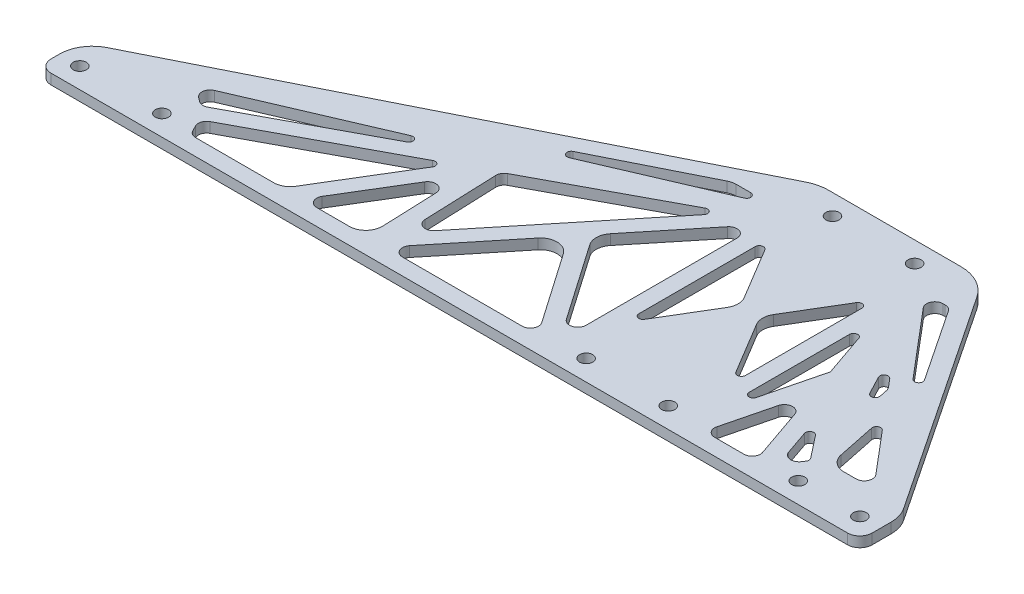
SolidWorks part; units mm, degrees
ref_plane "Front Plane" through (0, 0, 0) normal (0, 0, 1) x (1, 0, 0)
ref_plane "Top Plane" through (0, 0, 0) normal (0, 1, 0) x (1, 0, 0)
ref_plane "Right Plane" through (0, 0, 0) normal (1, 0, 0) x (0, 0, -1)
sketch "Sketch1" plane through (0, 0, 0) normal (0, 1, 0) x (1, 0, 0)
  line L0 (0, 0) -> (254, 0)
  line L2 (203.2, 88.9) -> (152.4, 88.9)
  line L4 (0, 0) -> (0, 12.7)
  line L5 (0, 12.7) -> (152.4, 88.9)
  line L6 (203.2, 88.9) -> (254, 12.7)
  line L7 (254, 12.7) -> (254, 0)
  line L8 (0, 6.35) -> (41.2306, 6.35) construction
  line L9 (254, 6.35) -> (220.1675, 6.35) construction
  line L10 (139.7, 82.55) -> (207.4333, 82.55) construction
  line L11 (156.6333, 76.2) -> (38.0113, 12.7) construction
  line L12 (38.0113, 12.7) -> (22.7185, 24.0592)
  line L13 (226.5259, 15.8112) -> (251.9259, 15.8112)
  line L20 (127, 76.2) -> (211.6667, 76.2)
  line L21 (226.5259, 15.8112) -> (215.9, 0)
  line L22 (38.0113, 12.7) -> (44.45, 0)
  line L23 (156.6333, 76.2) -> (27.2885, 20.6647) construction
  line L24 (156.6333, 76.2) -> (98.8302, 5.08) construction
  line L28 (194.7333, 76.2) -> (226.5259, 15.8112) construction
  line L31 (5.08, 9.5604) -> (153.5992, 83.82)
  line L32 (200.4813, 83.82) -> (153.5992, 83.82)
  line L33 (200.4813, 83.82) -> (248.92, 11.1619)
  line L34 (248.92, 11.1619) -> (248.92, 5.08)
  line L35 (5.08, 5.08) -> (248.92, 5.08)
  line L36 (5.08, 5.08) -> (5.08, 9.5604)
  line L37 (219.314, 5.08) -> (194.7333, 76.2) construction
  line L39 (194.7333, 76.2) -> (245.8205, 15.8112) construction
  line L40 (98.8302, 5.08) -> (97.3223, 44.45) construction
  line L41 (127.7318, 40.64) -> (152.3892, 5.08) construction
  line L42 (207.0237, 40.64) -> (198.1092, 5.08) construction
  line L83 (226.5259, 15.8112) -> (220.2769, 46.0056) construction
  line L84 (207.0237, 40.64) -> (226.5259, 15.8112) construction
  line L107 (97.3223, 44.45) -> (73.4302, 5.08) construction
  line L108 (156.6333, 76.2) -> (194.7333, 12.7) construction
  line L113 (194.7333, 76.2) -> (156.6333, 12.7) construction
  line L114 (155.6312, 78.534) -> (26.2864, 22.9986)
  line L115 (155.4346, 78.4393) -> (36.8125, 14.9393)
  line L116 (154.6622, 77.802) -> (101.1104, 11.9127)
  line L117 (156.6333, 12.7) -> (154.0933, 8.1397)
  line L118 (156.6333, 12.7) -> (194.7333, 12.7)
  line L119 (194.7333, 12.7) -> (200.3598, 0)
  line L120 (153.0965, 6.35) -> (197.5465, 6.35) construction
  line L123 (101.1104, 11.9127) -> (99.5369, 52.9951)
  line L124 (99.5369, 52.9951) -> (96.1931, 47.4852)
  line L125 (125.6445, 39.1927) -> (150.3019, 3.6327)
  line L126 (192.5553, 77.5068) -> (154.4553, 14.0068)
  line L127 (154.4553, 74.8932) -> (192.5553, 11.3932)
  line L128 (156.6333, 12.7) -> (156.6333, 76.2) construction
  line L129 (194.7333, 12.7) -> (194.7333, 76.2) construction
  line L130 (197.2733, 12.7) -> (197.2733, 76.2)
  line L131 (159.1733, 12.7) -> (159.1733, 76.2)
  line L132 (192.1933, 12.7) -> (192.1933, 76.2)
  line L133 (154.0933, 12.7) -> (154.0933, 76.2)
  line L134 (205.8201, 46.2844) -> (228.5234, 17.3801)
  line L137 (205.8201, 46.2844) -> (195.6454, 5.6976)
  line L138 (221.7147, 5.9097) -> (197.134, 77.0297)
  line L139 (192.4858, 75.0167) -> (224.2783, 14.6279)
  line L140 (229.0132, 16.3259) -> (222.7642, 46.5203)
  line L141 (157.6354, 73.866) -> (28.2906, 18.3307)
  line L142 (157.8321, 73.9607) -> (39.21, 10.4607)
  line L143 (158.6044, 74.598) -> (96.5501, -1.7527)
  line L144 (96.5501, -1.7527) -> (95.1077, 35.9049)
  line L145 (95.1077, 35.9049) -> (75.6017, 3.7622)
  line L146 (129.8191, 42.0873) -> (154.4765, 6.5273)
  line L147 (196.9114, 74.8932) -> (158.8114, 11.3932)
  line L148 (158.8114, 77.5068) -> (196.9114, 14.0068)
  line L149 (208.2273, 34.9956) -> (224.5284, 14.2422)
  line L150 (208.2273, 34.9956) -> (200.5729, 4.4624)
  line L151 (216.9134, 4.2503) -> (192.3327, 75.3703)
  line L152 (196.9809, 77.3833) -> (228.7734, 16.9944)
  line L153 (224.0386, 15.2964) -> (217.7896, 45.4908)
  line L154 (71.2588, 6.3978) -> (70.4591, 5.08)
  line L155 (36.8125, 14.9393) -> (35.7571, 14.3744)
  line L156 (39.21, 10.4607) -> (39.1601, 10.434)
  line L157 (154.0933, 12.7) -> (154.0933, 7.0799)
  line L158 (197.2733, 12.7) -> (197.2733, 6.9667)
  line L159 (224.5284, 14.2422) -> (225.0366, 13.5952)
  line L160 (229.0132, 16.3259) -> (229.1197, 15.8112)
  line L161 (192.7942, 74.5595) -> (243.8813, 14.1707)
  line L162 (196.6725, 77.8405) -> (247.7597, 17.4517)
  line L163 (153.766, 7.552) -> (149.5598, 0)
  line L164 (95.5112, 46.3615) -> (71.2588, 6.3978)
  line L165 (99.5369, 52.9951) -> (71.2588, 6.3978) construction
  circle A0 centre (6.35, 6.35) radius 2.032
  circle A1 centre (31.75, 6.35) radius 2.032
  circle A2 centre (228.6, 6.35) radius 2.032
  circle A3 centre (247.65, 6.35) radius 2.032
  circle A4 centre (162.9833, 82.55) radius 2.032
  circle A5 centre (188.3833, 82.55) radius 2.032
  circle A28 centre (162.9833, 6.35) radius 2.032
  circle A29 centre (188.3833, 6.35) radius 2.032
  arc A32 (197.2733, 12.7) -> (192.1933, 12.7) centre (194.7333, 12.7) cw
  arc A33 (197.2733, 76.2) -> (192.1933, 76.2) centre (194.7333, 76.2) ccw
  arc A34 (159.1733, 12.7) -> (154.0933, 12.7) centre (156.6333, 12.7) cw
  arc A35 (159.1733, 76.2) -> (154.0933, 76.2) centre (156.6333, 76.2) ccw
  arc A37 (155.6312, 78.534) -> (157.6354, 73.866) centre (156.6333, 76.2) cw
  arc A38 (26.2864, 22.9986) -> (28.2906, 18.3307) centre (27.2885, 20.6647) ccw
  arc A39 (155.4346, 78.4393) -> (157.8321, 73.9607) centre (156.6333, 76.2) cw
  arc A40 (36.8125, 14.9393) -> (39.21, 10.4607) centre (38.0113, 12.7) ccw
  arc A41 (154.6622, 77.802) -> (158.6044, 74.598) centre (156.6333, 76.2) cw
  arc A42 (71.2588, 6.3978) -> (75.6017, 3.7622) centre (73.4302, 5.08) ccw
  arc A43 (125.6445, 39.1927) -> (129.8191, 42.0873) centre (127.7318, 40.64) cw
  arc A44 (150.3019, 3.6327) -> (154.4765, 6.5273) centre (152.3892, 5.08) ccw
  arc A45 (192.5553, 77.5068) -> (196.9114, 74.8932) centre (194.7333, 76.2) cw
  arc A46 (154.4553, 14.0068) -> (158.8114, 11.3932) centre (156.6333, 12.7) ccw
  arc A47 (154.4553, 74.8932) -> (158.8114, 77.5068) centre (156.6333, 76.2) cw
  arc A48 (192.5553, 11.3932) -> (196.9114, 14.0068) centre (194.7333, 12.7) ccw
  arc A49 (228.5234, 17.3801) -> (224.5284, 14.2422) centre (226.5259, 15.8112) cw
  arc A50 (195.6454, 5.6976) -> (200.5729, 4.4624) centre (198.1092, 5.08) ccw
  arc A51 (221.7147, 5.9097) -> (216.9134, 4.2503) centre (219.314, 5.08) cw
  arc A52 (197.134, 77.0297) -> (192.3327, 75.3703) centre (194.7333, 76.2) ccw
  arc A53 (192.4858, 75.0167) -> (196.9809, 77.3833) centre (194.7333, 76.2) cw
  arc A54 (224.2783, 14.6279) -> (228.7734, 16.9944) centre (226.5259, 15.8112) ccw
  arc A55 (229.0132, 16.3259) -> (224.0386, 15.2964) centre (226.5259, 15.8112) cw
  arc A56 (222.7642, 46.5203) -> (217.7896, 45.4908) centre (220.2769, 46.0056) ccw
  arc A57 (192.7942, 74.5595) -> (196.6725, 77.8405) centre (194.7333, 76.2) cw
  arc A58 (243.8813, 14.1707) -> (247.7597, 17.4517) centre (245.8205, 15.8112) ccw
  point P113 (224.6364, 14.1137)
  point P115 (229.0402, 16.1718)
  point P129 (154.0933, 7.62)
  point P130 (154.2115, 7.8563)
  point P131 (0, 0)
  point P134 (0, 0)
  point P135 (0, 0)
  point P136 (153.4583, 6.35)
  dimension "D7" = 4.064
  dimension "D8" = 25.4
  dimension "D9" = 6.35
  dimension "D10" = 19.05
  dimension "D11" = 6.35
  dimension "D13" = 19.05
  dimension "D1" = 254
  dimension "D2" = 50.8
  dimension "D3" = 88.9
  dimension "D4" = 152.4
  dimension "D5" = 12.7
  dimension "D6" = 6.35
  dimension "D12" = 25.4
  dimension "D14" = 44.45
  dimension "D15" = 19.05
  dimension "D16" = 25.4
  dimension "D18" = 12.7
  dimension "D19" = 38.1
  dimension "D20" = 19.05
  dimension "D21" = 12.7
  dimension "D22" = 25.4
  dimension "D23" = 50.8
  dimension "D24" = 25.4
  dimension "D29" = 6.35
  dimension "D30" = 38.1
  dimension "D31" = 25.4
  dimension "D32" = 6.35
  dimension "D33" = 2.54
  dimension "D34" = 50.8
  dimension "D35" = 7.552
  dimension "D17" = 5.08
  dimension "D25" = 2.54
  dimension "D26" = 2.54
  dimension "D27" = 2.54
  dimension "D28" = 2.54
  dimension "D37" = 2.54
extrude "Boss-Extrude1" add sketch "Sketch1" along normal blind 3.175 contours L0 L7 L6 L2 L5 L4 | A0 | A1 | A5 | A4 | A2 | A3
extrude "Cut-Extrude2" cut sketch "Sketch1<3>" along normal through all contours L142 L156 L22 L35 L154 L124 | L155 L115 L124 L141 L12 | L144 L145 L35 | L116 L142 L123 | L125 L143 L35 | L157 L133 L143 L146 L117 | L114 L20 L31 | L130 L158 L137 L151 | L35 L151 L150 | L161 L152 L153 | L161 L140 L160 L13 | L159 L149 L138 L21 | L20 L162 L33 | L131 L126 L127 | L147 L148 L132 | L115 L141 L123 | A28 | A29 region at (64.7257, 0, -16.4796) region at (89.2658, 0, -15.355) region at (126.3241, 0, -15.5249) region at (118.3245, 0, -64.21) region at (56.1323, 0, -27.8913) region at (146.3644, 0, -38.8822) region at (115.9087, 0, -40.9571) region at (100.9162, 0, -49.3843) region at (212.3574, 0, -62.2554) region at (208.2553, 0, -13.9673) region at (220.1621, 0, -16.1676) region at (199.6409, 0, -37.9304) region at (163.6893, 0, -44.45) region at (232.1338, 0, -22.7875) region at (215.3763, 0, -44.8583) region at (187.6774, 0, -44.45)
sketch "Sketch1<3>" plane through (0, 0, 0) normal (0, 1, 0) x (1, 0, 0) same geometry as "Sketch1"
fillet "Fillet1" radius 3.81 2 edges at (254, 1.5875, 0) (0, 1.5875, 0)
fillet "Fillet2" radius 10.16 2 edges at (254, 1.5875, -12.7) (0, 1.5875, -12.7)
fillet "Fillet3" radius 12.7 2 edges at (203.2, 1.5875, -88.9) (152.4, 1.5875, -88.9)
fillet "Fillet4" radius 1.27 17 edges at (214.3608, 1.5875, -27.1869) (233.4505, 1.5875, -34.3662) (207.8157, 1.5875, -56.8029) (220.3926, 1.5875, -32.9136) (197.2733, 1.5875, -61.0753) (197.2733, 1.5875, -12.1914) (159.1733, 1.5875, -67.0298) (192.1933, 1.5875, -67.0298) (192.1933, 1.5875, -21.8702) (159.1733, 1.5875, -21.8702) (146.6944, 1.5875, -67.9985) (66.4191, 1.5875, -40.2299) (150.1953, 1.5875, -76.2) (224.7883, 1.5875, -36.74) (103.3533, 1.5875, -50.5595) (90.3319, 1.5875, -37.8269) (225.0366, 1.5875, -13.5952)
fillet "Fillet5" radius 2.54 20 edges at (39.1601, 1.5875, -10.434) (41.8745, 1.5875, -5.08) (99.9212, 1.5875, -42.9602) (101.1104, 1.5875, -11.9127) (95.1077, 1.5875, -35.9049) (76.4014, 1.5875, -5.08) (35.7571, 1.5875, -14.3744) (29.6468, 1.5875, -18.913) (198.0603, 1.5875, -76.2) (205.5613, 1.5875, -76.2) (217.9205, 1.5875, -44.8583) (242.4935, 1.5875, -15.8112) (221.0887, 1.5875, -7.7208) (216.6266, 1.5875, -5.08) (200.7278, 1.5875, -5.08) (207.4116, 1.5875, -31.7419) (154.0933, 1.5875, -69.0476) (149.2983, 1.5875, -5.08) (102.1034, 1.5875, -5.08) (154.0933, 1.5875, -7.0799)
fillet "Fillet6" radius 5.08 8 edges at (229.1197, 1.5875, -15.8112) (96.2884, 1.5875, -5.08) (172.7212, 1.5875, -44.45) (178.6455, 1.5875, -44.45) (130.9066, 1.5875, -40.519) (127.5708, 1.5875, -36.4147) (138.3592, 1.5875, -76.2) (70.4591, 1.5875, -5.08)
